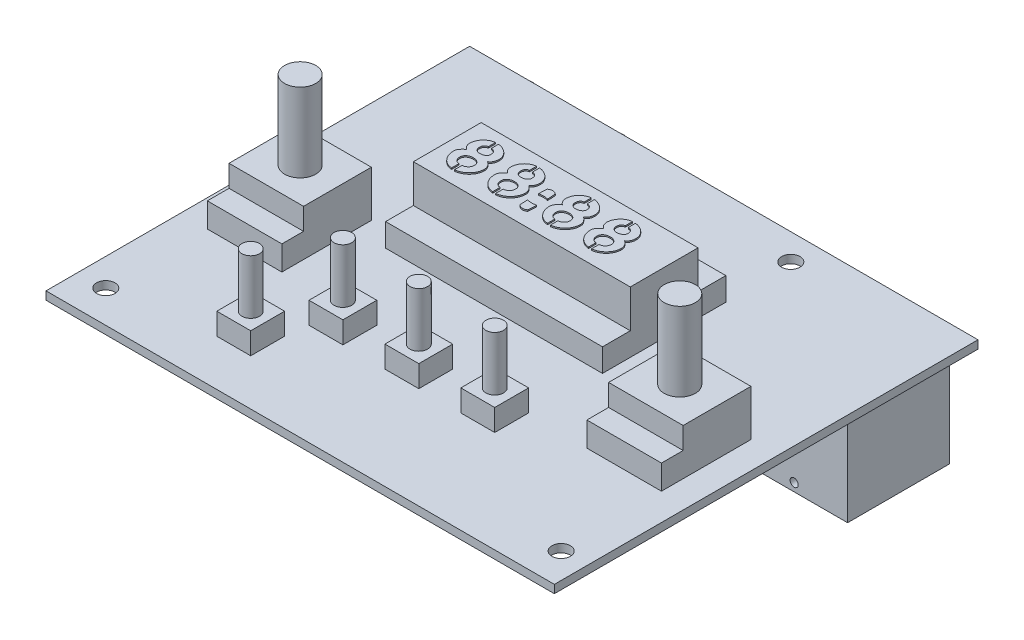
SolidWorks part; units mm, degrees
ref_plane "Front Plane" through (0, 0, 0) normal (0, 0, 1) x (1, 0, 0)
ref_plane "Top Plane" through (0, 0, 0) normal (0, 1, 0) x (1, 0, 0)
ref_plane "Right Plane" through (0, 0, 0) normal (1, 0, 0) x (0, 0, -1)
sketch "Sketch1" plane through (0, 0, 0) normal (0, 1, 0) x (1, 0, 0)
  line L1 (-47.625, 39.6875) -> (47.625, 39.6875)
  line L2 (-47.625, 39.6875) -> (-47.625, -39.6875)
  line L3 (-47.625, -39.6875) -> (47.625, -39.6875)
  line L4 (47.625, 39.6875) -> (47.625, -39.6875)
  line L5 (-47.625, 39.6875) -> (47.625, -39.6875) construction
  line L6 (-47.625, -39.6875) -> (47.625, 39.6875) construction
  point P0 (0, 0)
  dimension "D1" = 95.25
  dimension "D2" = 79.375
extrude "Boss-Extrude1" add sketch "Sketch1" along normal blind 1.524
hole_wizard "#29 (0.136) Diameter Hole1" positions "Sketch2" profile "Sketch3" hole size "#29" standard "ANSI Inch" end condition through all
sketch "Sketch2" plane through (0, 1.524, 0) normal (0, 1, 0) x (1, 0, 0)
  line L0 (47.625, -39.6875) -> (47.625, 39.6875) construction
  line L1 (-47.625, -39.6875) -> (47.625, -39.6875) construction
  line L2 (-47.625, 39.6875) -> (-47.625, -39.6875) construction
  line L3 (47.625, 39.6875) -> (-47.625, 39.6875) construction
  point P0 (42.8498, -33.6423)
  point P2 (17.4498, 34.7853)
  point P4 (-25.8318, 22.2123)
  point P6 (-42.4688, -33.6423)
  dimension "D1" = 4.7752
  dimension "D2" = 6.0452
  dimension "D3" = 6.0452
  dimension "D4" = 5.1562
  dimension "D5" = 30.1752
  dimension "D6" = 4.9022
  dimension "D7" = 17.4752
  dimension "D8" = 21.7932
sketch "Sketch3" plane through (42.8498, 1.524, 33.6423) normal (1, 0, 0) x (0, 0, 1)
  line L0 (0, 0) -> (0, 1.524)
  line L1 (0, 1.524) -> (1.7272, 1.524)
  line L2 (1.7272, 1.524) -> (1.7272, 0)
  line L5 (1.7272, 0) -> (0, 0)
  line L11 (0, -6.35) -> (0, 107.95) construction
  dimension "Thru Hole Dia." = 3.4544
  dimension "Thru Hole Depth" = 1.524
sketch "Sketch4" plane through (0, 1.524, 0) normal (0, 1, 0) x (1, 0, 0)
  line L0 (47.625, -39.6875) -> (47.625, 39.6875) construction
  line L1 (28.575, 2.2225) -> (42.545, 2.2225)
  line L2 (28.575, 2.2225) -> (28.575, -14.5415)
  line L3 (28.575, -14.5415) -> (42.545, -14.5415)
  line L4 (42.545, 2.2225) -> (42.545, -14.5415)
  line L5 (28.575, 2.2225) -> (42.545, -14.5415) construction
  line L6 (28.575, -14.5415) -> (42.545, 2.2225) construction
  line L7 (-47.625, -39.6875) -> (47.625, -39.6875) construction
  line L9 (-28.575, 2.2225) -> (-42.545, 2.2225)
  line L10 (-28.575, 2.2225) -> (-28.575, -14.5415)
  line L11 (-28.575, -14.5415) -> (-42.545, -14.5415)
  line L12 (-42.545, 2.2225) -> (-42.545, -14.5415)
  line L13 (-28.575, 2.2225) -> (-42.545, -14.5415) construction
  line L14 (-28.575, -14.5415) -> (-42.545, 2.2225) construction
  line L15 (-47.625, 39.6875) -> (-47.625, -39.6875) construction
  point P0 (35.56, -6.1595)
  point P9 (-35.56, -6.1595)
  dimension "D1" = 16.764
  dimension "D2" = 13.97
  dimension "D3" = 19.05
  dimension "D4" = 41.91
  dimension "D5" = 41.91
  dimension "D6" = 19.05
extrude "Boss-Extrude2" add sketch "Sketch4" along normal blind 4.572
sketch "Sketch5" plane through (0, 6.096, 0) normal (0, 1, 0) x (1, 0, 0)
  line L0 (-28.575, -14.5415) -> (-28.575, 2.2225) construction
  line L1 (-42.545, 2.2225) -> (-28.575, 2.2225)
  line L2 (-42.545, 2.2225) -> (-42.545, -10.4775)
  line L3 (-42.545, -10.4775) -> (-28.575, -10.4775)
  line L4 (-28.575, 2.2225) -> (-28.575, -10.4775)
  line L5 (42.545, -14.5415) -> (42.545, 2.2225) construction
  line L6 (28.575, 2.2225) -> (42.545, 2.2225)
  line L7 (28.575, 2.2225) -> (28.575, -10.4775)
  line L8 (28.575, -10.4775) -> (42.545, -10.4775)
  line L9 (42.545, 2.2225) -> (42.545, -10.4775)
  line L10 (0, 39.6875) -> (0, -39.6875) construction
  line L11 (47.625, 39.6875) -> (-47.625, 39.6875) construction
  line L12 (-47.625, -39.6875) -> (47.625, -39.6875) construction
  line L33 (-42.545, 2.2225) -> (-42.545, -14.5415) construction
  dimension "D1" = 12.7
extrude "Boss-Extrude3" add sketch "Sketch5" along normal blind 4.064
sketch "Sketch8" plane through (0, 1.524, 0) normal (0, 1, 0) x (1, 0, 0)
  line L0 (0, 39.6875) -> (0, -39.6875) construction
  line L1 (47.625, 39.6875) -> (-47.625, 39.6875) construction
  line L2 (-47.625, -39.6875) -> (47.625, -39.6875) construction
  line L3 (-47.625, 39.6875) -> (-47.625, -39.6875) construction
  line L5 (-24.257, -31.0515) -> (-17.907, -31.0515)
  line L6 (-24.257, -31.0515) -> (-24.257, -24.7015)
  line L7 (-24.257, -24.7015) -> (-17.907, -24.7015)
  line L8 (-3.175, -14.2875) -> (3.175, -20.6375) construction
  line L9 (-3.175, -20.6375) -> (3.175, -14.2875) construction
  line L10 (17.399, -14.2875) -> (17.399, -20.6375)
  line L11 (11.049, -14.2875) -> (17.399, -14.2875)
  line L12 (11.049, -14.2875) -> (11.049, -20.6375)
  line L13 (11.049, -20.6375) -> (17.399, -20.6375)
  line L14 (3.175, -14.2875) -> (3.175, -20.6375)
  line L15 (-3.175, -14.2875) -> (3.175, -14.2875)
  line L16 (-3.175, -14.2875) -> (-3.175, -20.6375)
  line L17 (-3.175, -20.6375) -> (3.175, -20.6375)
  line L18 (-11.049, -14.2875) -> (-11.049, -20.6375)
  line L19 (-17.399, -14.2875) -> (-11.049, -14.2875)
  line L20 (-17.399, -14.2875) -> (-17.399, -20.6375)
  line L21 (-17.399, -20.6375) -> (-11.049, -20.6375)
  line L22 (-17.907, -31.0515) -> (-17.907, -24.7015)
  line L23 (-24.257, -31.0515) -> (-17.907, -24.7015) construction
  line L24 (-24.257, -24.7015) -> (-17.907, -31.0515) construction
  point P6 (0, -17.4625)
  point P13 (-21.082, -27.8765)
  dimension "D1" = 30.226
  dimension "D2" = 58.674
  dimension "D3" = 6.35
  dimension "D4" = 53.975
  dimension "D5" = 29.718
  dimension "D6" = 14.986
extrude "Boss-Extrude5" add sketch "Sketch8" along normal blind 4.064
sketch "Sketch9" plane through (0, 5.588, 0) normal (0, 1, 0) x (1, 0, 0)
  line L0 (-24.257, -24.7015) -> (-17.907, -31.0515) construction
  line L1 (-17.399, -14.2875) -> (-11.049, -20.6375) construction
  line L3 (-17.399, -20.6375) -> (-11.049, -20.6375) construction
  line L7 (-11.049, -20.6375) -> (-11.049, -14.2875) construction
  line L9 (-3.175, -14.2875) -> (3.175, -20.6375) construction
  line L10 (11.049, -14.2875) -> (17.399, -20.6375) construction
  circle A0 centre (-21.082, -27.8765) radius 1.651
  circle A1 centre (-14.224, -17.4625) radius 1.651
  circle A2 centre (0, -17.4625) radius 1.651
  circle A3 centre (14.224, -17.4625) radius 1.651
  dimension "D1" = 3.302
extrude "Boss-Extrude6" add sketch "Sketch9" along normal blind 10.16
sketch "Sketch10" plane through (0, 10.16, 0) normal (0, 1, 0) x (1, 0, 0)
  line L0 (-42.545, 2.2225) -> (-28.575, -10.4775) construction
  line L1 (28.575, 2.2225) -> (42.545, -10.4775) construction
  circle A0 centre (-35.56, -4.1275) radius 2.921
  circle A1 centre (35.56, -4.1275) radius 2.921
  dimension "D1" = 5.842
extrude "Boss-Extrude7" add sketch "Sketch10" along normal blind 14.732
sketch "Sketch11" plane through (0, 0, -39.6875) normal (0, 0, -1) x (-1, 0, 0)
  line L0 (-47.625, 0) -> (47.625, 0) construction
  line L1 (-42.2402, 0) -> (-22.225, 0)
  line L2 (-42.2402, 0) -> (-42.2402, -21.336)
  line L3 (-42.2402, -21.336) -> (-22.225, -21.336)
  line L4 (-22.225, 0) -> (-22.225, -21.336)
  line L5 (-47.625, 1.524) -> (-47.625, 0) construction
  dimension "D1" = 25.4
  dimension "D2" = 20.0152
  dimension "D3" = 21.336
extrude "Boss-Extrude8" add sketch "Sketch11" against normal blind 19.05 separate body
sketch "Sketch12" plane through (0, 0, -39.6875) normal (0, 0, -1) x (-1, 0, 0)
  line L0 (-32.2326, 0) -> (-32.2326, -21.336) construction
  line L1 (-22.225, 0) -> (-42.2402, 0) construction
  line L2 (-42.2402, -21.336) -> (-22.225, -21.336) construction
  circle A0 centre (-32.2326, -10.541) radius 6.985
  dimension "D1" = 13.97
  dimension "D2" = 10.795
extrude "Cut-Extrude1" cut sketch "Sketch12" against normal blind 3.175
hole_wizard "#53 (0.0595) Diameter Hole1" positions "Sketch13" profile "Sketch14" hole size "#53" standard "ANSI Inch" end condition through all
sketch "Sketch13" plane through (0, 0, -39.6875) normal (0, 0, -1) x (-1, 0, 0)
  line L1 (-32.2326, -10.541) -> (-32.2326, -21.336) construction
  line L2 (-42.2402, -21.336) -> (-22.225, -21.336) construction
  line L3 (-23.4886, -5.4927) -> (-32.2326, -10.541) construction
  line L5 (-40.9765, -5.4927) -> (-32.2326, -10.541) construction
  line L7 (-22.225, -21.336) -> (-22.225, 0) construction
  line L8 (-42.2402, 0) -> (-42.2402, -21.336) construction
  point P0 (-40.9765, -5.4927)
  point P2 (-23.4886, -5.4927)
  point P14 (-32.2326, -19.8183)
  dimension "D1" = 1.5176
  dimension "D2" = 120
  dimension "D3" = 120
  dimension "D4" = 1.2637
  dimension "D5" = 1.2637
sketch "Sketch14" plane through (40.9765, -5.4927, -39.6875) normal (1, 0, 0) x (0, 1, 0)
  line L0 (0, 0) -> (0, 79.375)
  line L1 (0, 79.375) -> (0.7556, 79.375)
  line L2 (0.7556, 79.375) -> (0.7556, 0)
  line L5 (0.7556, 0) -> (0, 0)
  line L11 (0, -6.35) -> (0, 107.95) construction
  dimension "Thru Hole Dia." = 1.5113
  dimension "Thru Hole Depth" = 79.375
sketch "Sketch15" plane through (0, 0, -39.6875) normal (0, 0, -1) x (-1, 0, 0)
  line L0 (-47.625, 0) -> (47.625, 0) construction
  line L1 (34.925, 0) -> (40.894, 0)
  line L2 (34.925, 0) -> (34.925, -5.334)
  line L3 (34.925, -5.334) -> (40.894, -5.334)
  line L4 (40.894, 0) -> (40.894, -5.334)
  line L5 (47.625, 1.524) -> (47.625, 0) construction
  line L7 (17.8816, 0) -> (23.8506, 0)
  line L8 (17.8816, 0) -> (17.8816, -5.334)
  line L9 (17.8816, -5.334) -> (23.8506, -5.334)
  line L10 (23.8506, 0) -> (23.8506, -5.334)
  dimension "D1" = 5.969
  dimension "D2" = 5.334
  dimension "D3" = 12.7
  dimension "D4" = 11.0744
extrude "Boss-Extrude9" add sketch "Sketch15" against normal blind 13.97
sketch "Sketch16" plane through (0, 0, -39.6875) normal (0, 0, -1) x (-1, 0, 0)
  line L0 (34.925, 0) -> (40.894, -5.334) construction
  line L1 (17.8816, 0) -> (23.8506, -5.334) construction
  circle A0 centre (37.9095, -2.667) radius 1.778
  circle A1 centre (37.9095, -2.667) radius 2.54
  circle A2 centre (20.8661, -2.667) radius 1.778
  circle A3 centre (20.8661, -2.667) radius 2.54
  dimension "D1" = 5.08
  dimension "D2" = 3.556
extrude "Boss-Extrude10" add sketch "Sketch16" along normal blind 2.032 draft 9
sketch "Sketch17" plane through (0, 0, -39.6875) normal (0, 0, -1) x (-1, 0, 0)
  circle A0 centre (37.9095, -2.667) radius 1.778
  circle A1 centre (20.8661, -2.667) radius 1.778
extrude "Cut-Extrude2" cut sketch "Sketch17" against normal blind 12.7
sketch "Sketch18" plane through (0, 1.524, 0) normal (0, 1, 0) x (1, 0, 0)
  line L0 (-47.625, 39.6875) -> (-47.625, -39.6875) construction
  line L1 (-22.733, -0.9525) -> (17.907, -0.9525)
  line L2 (-22.733, -0.9525) -> (-22.733, 22.1615)
  line L3 (-22.733, 22.1615) -> (17.907, 22.1615)
  line L4 (17.907, -0.9525) -> (17.907, 22.1615)
  line L5 (47.625, 39.6875) -> (-47.625, 39.6875) construction
  dimension "D1" = 40.64
  dimension "D2" = 23.114
  dimension "D3" = 65.532
  dimension "D4" = 40.64
extrude "Boss-Extrude11" add sketch "Sketch18" along normal blind 4.318
sketch "Sketch19" plane through (0, 5.842, 0) normal (0, 1, 0) x (1, 0, 0)
  line L0 (-22.733, 22.1615) -> (17.907, -0.9525) construction
  line L1 (17.907, -0.9525) -> (17.907, 22.1615) construction
  line L2 (-22.733, 4.2545) -> (17.907, 4.2545)
  line L3 (-22.733, 4.2545) -> (-22.733, 16.9545)
  line L4 (-22.733, 16.9545) -> (17.907, 16.9545)
  line L5 (17.907, 4.2545) -> (17.907, 16.9545)
  line L6 (-22.733, 4.2545) -> (17.907, 16.9545) construction
  line L7 (-22.733, 16.9545) -> (17.907, 4.2545) construction
  point P4 (-2.413, 10.6045)
  dimension "D1" = 12.7
extrude "Boss-Extrude12" add sketch "Sketch19" along normal blind 7.112
sketch "Sketch20" plane through (0, 0, 0) normal (0, -1, 0) x (1, 0, 0)
  line L0 (-47.625, 39.6875) -> (47.625, 39.6875) construction
  line L1 (17.653, 35.8775) -> (-15.367, 35.8775)
  line L2 (17.653, 35.8775) -> (17.653, 33.4675)
  line L3 (17.653, 33.4675) -> (-15.367, 33.4675)
  line L4 (-15.367, 35.8775) -> (-15.367, 33.4675)
  line L5 (47.625, 39.6875) -> (47.625, -39.6875) construction
  dimension "D1" = 33.02
  dimension "D2" = 2.41
  dimension "D3" = 3.81
  dimension "D4" = 29.972
extrude "Boss-Extrude13" add sketch "Sketch20" along normal blind 2.54
sketch "Sketch21" plane through (0, 0, 0) normal (0, -1, 0) x (1, 0, 0)
  line L0 (47.625, -39.6875) -> (-17.8816, -39.6875) construction
  line L1 (3.429, -39.6875) -> (-5.461, -39.6875)
  line L2 (3.429, -39.6875) -> (3.429, -35.1155)
  line L3 (3.429, -35.1155) -> (-5.461, -35.1155)
  line L4 (-5.461, -39.6875) -> (-5.461, -35.1155)
  line L5 (47.625, 39.6875) -> (47.625, -39.6875) construction
  dimension "D1" = 8.89
  dimension "D2" = 4.572
  dimension "D3" = 53.086
extrude "Boss-Extrude14" add sketch "Sketch21" along normal blind 4.826
sketch "Sketch22" plane through (0, 0, -39.6875) normal (0, 0, -1) x (-1, 0, 0)
  line L0 (40.894, -5.334) -> (40.894, 0) construction
  line L1 (5.461, -4.826) -> (5.461, 0) construction
  line L2 (-3.429, -3.429) -> (5.461, -3.429)
  line L3 (-3.429, -3.429) -> (-3.429, -1.397)
  line L4 (-3.429, -1.397) -> (5.461, -1.397)
  line L5 (5.461, -3.429) -> (5.461, -1.397)
  line L6 (-3.429, -3.429) -> (5.461, -1.397) construction
  line L7 (-3.429, -1.397) -> (5.461, -3.429) construction
  line L8 (34.925, -5.334) -> (40.894, -5.334) construction
  point P4 (1.016, -2.413)
  dimension "D1" = 2.032
  dimension "D2" = 39.878
  dimension "D3" = 1.905
extrude "Boss-Extrude15" add sketch "Sketch22" along normal blind 1.524
sketch "Sketch23" plane through (0, 12.954, 0) normal (0, 1, 0) x (1, 0, 0)
  line L0 (17.907, 4.2545) -> (17.907, 16.9545) construction
  line L1 (17.907, 16.9545) -> (-22.733, 16.9545) construction
  text T0 "88:88" font "Stencilia-Bold" height in points 25
  dimension "D1" = 39.3082
  dimension "D2" = 10.3887
extrude "Boss-Extrude16" add sketch "Sketch23" along normal blind 0.254
